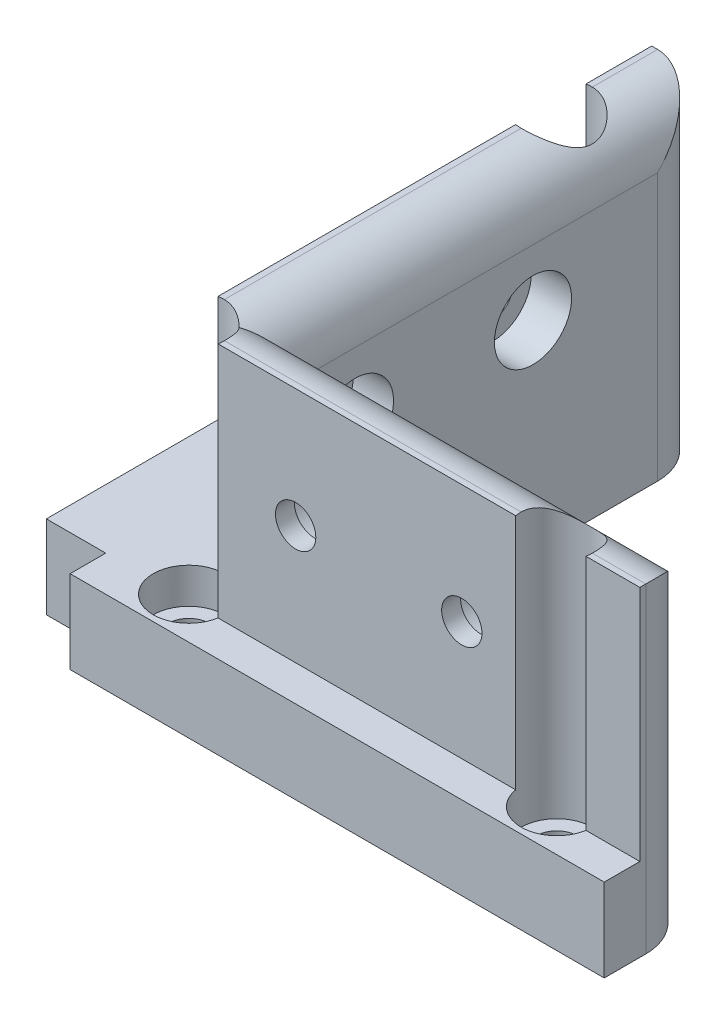
SolidWorks part; units mm, degrees
material "ABS"
ref_plane "Front Plane" through (0, 0, 0) normal (0, 0, 1) x (1, 0, 0)
ref_plane "Top Plane" through (0, 0, 0) normal (0, 1, 0) x (1, 0, 0)
ref_plane "Right Plane" through (0, 0, 0) normal (1, 0, 0) x (0, 0, -1)
sketch "Sketch1" plane through (0, 0, 0) normal (0, 1, 0) x (1, 0, 0)
  line L1 (0, 0) -> (45, 0)
  line L2 (0, 0) -> (0, 40)
  line L3 (0, 40) -> (45, 40)
  line L4 (45, 0) -> (45, 40)
  dimension "D1" = 45
  dimension "D2" = 40
extrude "Boss-Extrude1" add sketch "Sketch1" along normal blind 29
sketch "Sketch33" plane through (0, 29, 0) normal (0, 1, 0) x (1, 0, 0)
  line L0 (0, 40) -> (0, 0) construction
  line L1 (45, 0) -> (11, 0)
  line L2 (45, 0) -> (45, 35)
  line L3 (45, 35) -> (11, 35)
  line L4 (11, 0) -> (11, 35)
  line L5 (45, 40) -> (0, 40) construction
  dimension "D1" = 11
  dimension "D2" = 5
extrude "Cut-Extrude7" cut sketch "Sketch33" against normal through all
sketch "Sketch39" plane through (0, 0, -40) normal (0, 0, -1) x (-1, 0, 0)
  line L0 (0, 29) -> (0, 0) construction
  line L1 (-45, 0) -> (0, 0)
  line L2 (-45, 0) -> (-45, 9)
  line L3 (-45, 9) -> (0, 9)
  line L4 (0, 0) -> (0, 9)
  dimension "D1" = 9
extrude "Boss-Extrude2" add sketch "Sketch39" along normal blind 3
sketch "Sketch21" plane through (0, 29, 0) normal (0, 1, 0) x (1, 0, 0)
  line L0 (45, 40) -> (0, 40) construction
  circle A1 centre (6.5, 39.5) radius 1.75
  circle A2 centre (6.5, 8.5) radius 1.75
  circle A3 centre (37.5, 39.5) radius 1.75
  dimension "D3" = 0.5
  dimension "D4" = 3.5
  dimension "D7" = 3.5
  dimension "D8" = 3.5
  dimension "D1" = 0.5
  dimension "D2" = 31
extrude "Cut-Extrude6" cut sketch "Sketch21" against normal through all both and the other way through all
sketch "Sketch34" plane through (0, 29, 0) normal (0, 1, 0) x (1, 0, 0)
  circle A0 centre (6.5, 8.5) radius 3
  circle A1 centre (6.5, 39.5) radius 3
  circle A2 centre (37.5, 39.5) radius 3
  dimension "D1" = 6
  dimension "D2" = 6
  dimension "D3" = 6
extrude "Cut-Extrude8" cut sketch "Sketch34" against normal blind 23
hole_wizard "CBORE for M3 Hex Socket Head Cap Screw1" positions "Sketch35" profile "Sketch36" counterbore size "M3" standard "ISO" end condition through all
sketch "Sketch35" plane through (11, 0, 0) normal (1, 0, 0) x (0, 0, -1)
  line L1 (0, 0) -> (0, 29) construction
  line L2 (35, 0) -> (35, 29) construction
  line L3 (35, 29) -> (0, 29) construction
  point P0 (15, 19)
  point P2 (30, 19)
  dimension "D1" = 10
  dimension "D2" = 10
  dimension "D3" = 15
  dimension "D4" = 5
sketch "Sketch36" plane through (11, 19, -15) normal (0, 1, 0) x (0, 0, -1)
  line L0 (0, 0) -> (0, 11)
  line L1 (0, 11) -> (1.7, 11)
  line L3 (1.7, 11) -> (1.7, 3.4)
  line L4 (1.7, 3.4) -> (3.25, 3.4)
  line L5 (3.25, 3.4) -> (3.25, 0)
  line L7 (3.25, 0) -> (0, 0)
  line L11 (0, -6.35) -> (0, 107.95) construction
  dimension "Thru Hole Dia." = 3.4
  dimension "Thru Hole Depth" = 11
  dimension "C'Bore Dia." = 6.5
  dimension "C'Bore Depth" = 3.4
hole_wizard "CBORE for M3 Hex Socket Head Cap Screw2" positions "Sketch37" profile "Sketch38" counterbore size "M3" standard "ISO" end condition through all
sketch "Sketch37" plane through (0, 0, -35) normal (0, 0, 1) x (1, 0, 0)
  line L1 (11, 0) -> (11, 29) construction
  line L2 (45, 0) -> (45, 29) construction
  line L3 (45, 29) -> (11, 29) construction
  point P0 (16, 19)
  point P2 (30, 19)
  dimension "D1" = 10
  dimension "D2" = 10
  dimension "D3" = 5
  dimension "D4" = 15
sketch "Sketch38" plane through (16, 19, -35) normal (1, 0, 0) x (0, -1, 0)
  line L0 (0, 0) -> (0, 8)
  line L1 (0, 8) -> (1.7, 8)
  line L3 (1.7, 8) -> (1.7, 3.4)
  line L4 (1.7, 3.4) -> (3.25, 3.4)
  line L5 (3.25, 3.4) -> (3.25, 0)
  line L7 (3.25, 0) -> (0, 0)
  line L11 (0, -6.35) -> (0, 107.95) construction
  dimension "Thru Hole Dia." = 3.4
  dimension "Thru Hole Depth" = 8
  dimension "C'Bore Dia." = 6.5
  dimension "C'Bore Depth" = 3.4
fillet "Fillet1" radius 4.5 4 edges at (11, 14.5, 0) (45, 14.5, -35) (28, 29, -35) (11, 29, -17.5)
sketch "Sketch40" plane through (0, 0, 0) normal (-1, 0, 0) x (0, 0, 1)
  line L0 (-43, 0) -> (-43, 9) construction
  line L1 (-43, 2) -> (0, 2)
  line L2 (-43, 2) -> (-43, 0)
  line L3 (-43, 0) -> (0, 0)
  line L4 (0, 2) -> (0, 0)
  dimension "D1" = 2
extrude "Cut-Extrude9" cut sketch "Sketch40" against normal through all
sketch "Sketch41" plane through (0, 29, 0) normal (0, 1, 0) x (1, 0, 0)
  line L0 (3.542, 40) -> (0, 40) construction
  line L1 (0, 0) -> (6, 0)
  line L2 (0, 0) -> (0, 40)
  line L3 (0, 40) -> (6, 40)
  line L4 (6, 0) -> (6, 40)
  dimension "D1" = 6
extrude "Cut-Extrude10" cut sketch "Sketch41" against normal blind 20
sketch "Sketch42" plane through (0, 0, 0) normal (-1, 0, 0) x (0, 0, 1)
  line L0 (0, 2) -> (-43, 2) construction
  line L1 (0, 9) -> (-40, 9)
  line L2 (0, 9) -> (0, 2)
  line L3 (0, 2) -> (-40, 2)
  line L4 (-40, 9) -> (-40, 2)
  line L5 (-43, 2) -> (-43, 9) construction
  dimension "D1" = 3
extrude "Boss-Extrude3" add sketch "Sketch42" along normal blind 5
mirror "Mirror1" about plane through (0, 29, 0) normal (0, 0, -1) of bodies 127 122
delete or keep bodies "Body-Delete/Keep 1" type delete bodies bodies 127
